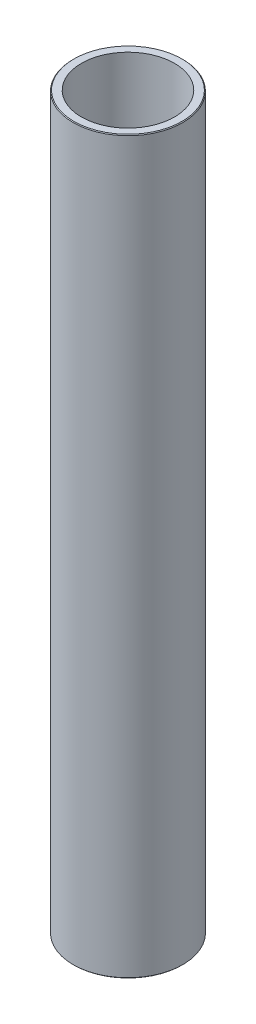
SolidWorks part; units mm, degrees
ref_plane "Front Plane" through (0, 0, 0) normal (0, 0, 1) x (1, 0, 0)
ref_plane "Top Plane" through (0, 0, 0) normal (0, 1, 0) x (1, 0, 0)
ref_plane "Right Plane" through (0, 0, 0) normal (1, 0, 0) x (0, 0, -1)
sketch "Sketch1" plane through (0, 0, 0) normal (0, 1, 0) x (1, 0, 0)
  circle A0 centre (0, 0) radius 45
  dimension "SHAFT_OD" = 90
extrude "Boss-Extrude1" add sketch "Sketch1" along normal blind 600
sketch "Sketch2" plane through (0, 0, 0) normal (0, 1, 0) x (1, 0, 0)
  circle A0 centre (0, 0) radius 38.2205
  dimension "BORE_D" = 76.441
extrude "Cut-Extrude1" cut sketch "Sketch2" along normal through all
chamfer "Chamfer1" distance 0.5998 angle 45 2 edges at (0, 600, 45) (0, 0, 45)
